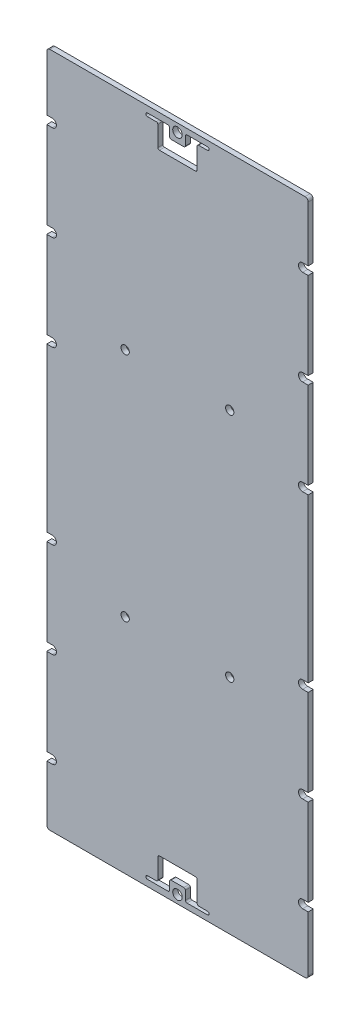
SolidWorks part; units mm, degrees
material "FR4_stuffedProtoboard"
ref_plane "Front Plane" through (0, 0, 0) normal (0, 0, 1) x (1, 0, 0)
ref_plane "Top Plane" through (0, 0, 0) normal (0, 1, 0) x (1, 0, 0)
ref_plane "Right Plane" through (0, 0, 0) normal (1, 0, 0) x (0, 0, -1)
sketch "Sketch1" plane through (0, 0, 0) normal (0, 0, 1) x (1, 0, 0)
  line L0 (-37, -97) -> (37, -97) construction
  line L5 (-37, -95.4) -> (37, -95.4) construction
  line L6 (-37, -87) -> (37, -87) construction
  line L7 (-37, -85.4) -> (37, -85.4) construction
  line L8 (-37, -77) -> (37, -77) construction
  line L9 (-37, -75.4) -> (37, -75.4) construction
  line L10 (-37, -67) -> (37, -67) construction
  line L11 (-37, -65.4) -> (37, -65.4) construction
  line L12 (-37, -57) -> (37, -57) construction
  line L13 (-37, -55.4) -> (37, -55.4) construction
  line L14 (-37, -47) -> (37, -47) construction
  line L15 (-37, -45.4) -> (37, -45.4) construction
  line L16 (-37, -37) -> (37, -37) construction
  line L17 (-37, -35.4) -> (37, -35.4) construction
  line L18 (-37, -27) -> (37, -27) construction
  line L19 (-37, -25.4) -> (37, -25.4) construction
  line L20 (-37, -17) -> (37, -17) construction
  line L21 (-37, -15.4) -> (37, -15.4) construction
  line L22 (-37, 15.4) -> (37, 15.4) construction
  line L23 (-37, 17) -> (37, 17) construction
  line L24 (-37, 25.4) -> (37, 25.4) construction
  line L25 (-37, 27) -> (37, 27) construction
  line L26 (-37, 35.4) -> (37, 35.4) construction
  line L27 (-37, 37) -> (37, 37) construction
  line L29 (-41.5, 107) -> (41.5, 107)
  line L30 (-41.5, 107) -> (-41.5, -107)
  line L31 (-41.5, -107) -> (41.5, -107)
  line L33 (41.5, 107) -> (41.5, -107)
  line L35 (-26.7, 107) -> (-28.3, 107) construction
  line L37 (-41.5, 109.5) -> (-41.5, 97.4) construction
  line L38 (41.5, 112.5) -> (41.5, 109.5) construction
  line L39 (-28.3, -107) -> (-26.7, -107) construction
  line L40 (-41.25, 106.75) -> (41.25, 106.75)
  line L41 (41.25, 106.75) -> (41.25, -106.75)
  line L42 (-41.25, -106.75) -> (41.25, -106.75)
  line L43 (-41.25, 106.75) -> (-41.25, -106.75)
  line L76 (-37, 45.4) -> (37, 45.4) construction
  line L77 (-37, 47) -> (37, 47) construction
  line L78 (-37, 55.4) -> (37, 55.4) construction
  line L79 (-37, 57) -> (37, 57) construction
  line L80 (-37, 65.4) -> (37, 65.4) construction
  line L81 (-37, 67) -> (37, 67) construction
  line L82 (-37, 75.4) -> (37, 75.4) construction
  line L83 (-37, 77) -> (37, 77) construction
  line L84 (-37, 85.4) -> (37, 85.4) construction
  line L85 (-37, 87) -> (37, 87) construction
  line L86 (-37, 95.4) -> (37, 95.4) construction
  line L87 (-37, 97) -> (37, 97) construction
  line L88 (-37, -97) -> (37, -97) construction
  line L89 (-37, -95.4) -> (37, -95.4) construction
  line L90 (-37, -87) -> (37, -87) construction
  line L91 (-37, -85.4) -> (37, -85.4) construction
  line L92 (-37, -77) -> (37, -77) construction
  line L93 (-37, -75.4) -> (37, -75.4) construction
  line L94 (-37, -67) -> (37, -67) construction
  line L95 (-37, -65.4) -> (37, -65.4) construction
  line L96 (-37, -57) -> (37, -57) construction
  line L97 (-37, -55.4) -> (37, -55.4) construction
  line L98 (-37, -47) -> (37, -47) construction
  line L99 (-37, -45.4) -> (37, -45.4) construction
  line L100 (-37, -37) -> (37, -37) construction
  line L101 (-37, -35.4) -> (37, -35.4) construction
  line L102 (-37, -27) -> (37, -27) construction
  line L103 (-37, -25.4) -> (37, -25.4) construction
  line L104 (-37, -17) -> (37, -17) construction
  line L105 (-37, -15.4) -> (37, -15.4) construction
  line L106 (-37, 15.4) -> (37, 15.4) construction
  line L107 (-37, 17) -> (37, 17) construction
  line L108 (-37, 25.4) -> (37, 25.4) construction
  line L109 (-37, 27) -> (37, 27) construction
  line L110 (-37, 35.4) -> (37, 35.4) construction
  line L111 (-37, 37) -> (37, 37) construction
  line L112 (-37, 45.4) -> (37, 45.4) construction
  line L113 (-37, 47) -> (37, 47) construction
  line L114 (-37, 55.4) -> (37, 55.4) construction
  line L115 (-37, 57) -> (37, 57) construction
  line L116 (-37, 65.4) -> (37, 65.4) construction
  line L117 (-37, 67) -> (37, 67) construction
  line L118 (-37, 75.4) -> (37, 75.4) construction
  line L119 (-37, 77) -> (37, 77) construction
  line L120 (-37, 85.4) -> (37, 85.4) construction
  line L121 (-37, 87) -> (37, 87) construction
  line L122 (-37, 95.4) -> (37, 95.4) construction
  line L123 (-37, 97) -> (37, 97) construction
  circle A0 centre (-39.5, 87) radius 0.8 construction
  circle A1 centre (-39.5, -27) radius 0.8 construction
  circle A2 centre (-39.5, 57) radius 0.8 construction
  circle A3 centre (39.5, -27) radius 0.8 construction
  circle A4 centre (-39.5, -27) radius 0.8
  circle A5 centre (-39.5, 27) radius 0.8 construction
  circle A6 centre (-16.5, 36.5) radius 0.8 construction
  circle A8 centre (39.5, -27) radius 0.8
  circle A9 centre (-16.5, -36.5) radius 0.8 construction
  circle A11 centre (-39.5, -57) radius 0.8 construction
  circle A13 centre (-39.5, -87) radius 0.8 construction
  circle A16 centre (0, -104.2) radius 0.8 construction
  circle A19 centre (39.5, -87) radius 0.8 construction
  circle A21 centre (39.5, -57) radius 0.8 construction
  circle A22 centre (16.5, -36.5) radius 0.8 construction
  circle A27 centre (39.5, 27) radius 0.8 construction
  circle A28 centre (16.5, 36.5) radius 0.8 construction
  circle A30 centre (39.5, 57) radius 0.8 construction
  circle A32 centre (39.5, 87) radius 0.8 construction
  circle A35 centre (0, 104.2) radius 0.8 construction
  circle A38 centre (-39.5, 87) radius 0.8
  circle A40 centre (-39.5, 57) radius 0.8
  circle A43 centre (-39.5, 27) radius 0.8
  circle A44 centre (-16.5, 36.5) radius 0.8
  circle A47 centre (-16.5, -36.5) radius 0.8
  circle A49 centre (-39.5, -57) radius 0.8
  circle A51 centre (-39.5, -87) radius 0.8
  circle A54 centre (0, -104.2) radius 0.8
  circle A57 centre (39.5, -87) radius 0.8
  circle A59 centre (39.5, -57) radius 0.8
  circle A60 centre (16.5, -36.5) radius 0.8
  circle A65 centre (39.5, 27) radius 0.8
  circle A66 centre (16.5, 36.5) radius 0.8
  circle A68 centre (39.5, 57) radius 0.8
  circle A70 centre (39.5, 87) radius 0.8
  circle A73 centre (0, 104.2) radius 0.8
  dimension "D1" = 0.25
extrude "pcb extrude" add sketch "Sketch1" along normal blind 1.6 contours A73 A70 A68 A66 A65 region at (0, 0, 0)
sketch "connector locations" plane through (0, 0, 1.6) normal (0, 0, 1) x (1, 0, 0)
  line L0 (-37, 97) -> (37, 97) construction
  line L1 (-33.9182, 100.556) -> (-9.2802, 100.556)
  line L2 (-33.9182, 100.556) -> (-33.9182, 99.159)
  line L3 (-33.9182, 99.159) -> (-9.2802, 99.159)
  line L4 (-9.2802, 100.556) -> (-9.2802, 99.159)
  line L5 (-33.9182, 100.556) -> (-9.2802, 99.159) construction
  line L6 (-33.9182, 99.159) -> (-9.2802, 100.556) construction
  line L7 (-37, 87) -> (37, 87) construction
  line L8 (-33.9182, 90.556) -> (-22.0818, 90.556)
  line L9 (-33.9182, 90.556) -> (-33.9182, 89.159)
  line L10 (-33.9182, 89.159) -> (-22.0818, 89.159)
  line L11 (-22.0818, 90.556) -> (-22.0818, 89.159)
  line L12 (-33.9182, 90.556) -> (-22.0818, 89.159) construction
  line L13 (-33.9182, 89.159) -> (-22.0818, 90.556) construction
  line L14 (0, -55) -> (0, 55) construction
  line L15 (-12.319, 90.556) -> (12.319, 90.556)
  line L16 (-12.319, 90.556) -> (-12.319, 89.159)
  line L17 (-12.319, 89.159) -> (12.319, 89.159)
  line L18 (12.319, 90.556) -> (12.319, 89.159)
  line L19 (-12.319, 90.556) -> (12.319, 89.159) construction
  line L20 (-12.319, 89.159) -> (12.319, 90.556) construction
  line L21 (-37, -85.4) -> (37, -85.4) construction
  line L22 (-33.9182, -91.844) -> (-9.2802, -91.844)
  line L23 (-33.9182, -91.844) -> (-33.9182, -93.241)
  line L24 (-33.9182, -93.241) -> (-9.2802, -93.241)
  line L25 (-9.2802, -91.844) -> (-9.2802, -93.241)
  line L26 (-33.9182, -91.844) -> (-9.2802, -93.241) construction
  line L27 (-33.9182, -93.241) -> (-9.2802, -91.844) construction
  line L28 (-33.9182, -81.844) -> (-22.0818, -81.844)
  line L29 (-33.9182, -81.844) -> (-33.9182, -83.241)
  line L30 (-33.9182, -83.241) -> (-22.0818, -83.241)
  line L31 (-22.0818, -81.844) -> (-22.0818, -83.241)
  line L32 (-33.9182, -81.844) -> (-22.0818, -83.241) construction
  line L33 (-33.9182, -83.241) -> (-22.0818, -81.844) construction
  line L34 (-12.319, -81.844) -> (12.319, -81.844)
  line L35 (-12.319, -81.844) -> (-12.319, -83.241)
  line L36 (-12.319, -83.241) -> (12.319, -83.241)
  line L37 (12.319, -81.844) -> (12.319, -83.241)
  line L38 (-12.319, -81.844) -> (12.319, -83.241) construction
  line L39 (-12.319, -83.241) -> (12.319, -81.844) construction
  line L40 (-37, -95.4) -> (37, -95.4) construction
  line L41 (-33.9182, 80.556) -> (-33.9182, 79.159)
  line L42 (-33.9182, 80.556) -> (-22.0818, 80.556)
  line L43 (-22.0818, 80.556) -> (-22.0818, 79.159)
  line L44 (-33.9182, 79.159) -> (-22.0818, 79.159)
  line L45 (-33.9182, 80.556) -> (-22.0818, 79.159) construction
  line L46 (-33.9182, 79.159) -> (-22.0818, 80.556) construction
  line L47 (-12.319, 80.556) -> (-12.319, 79.159)
  line L48 (-12.319, 80.556) -> (12.319, 80.556)
  line L49 (12.319, 80.556) -> (12.319, 79.159)
  line L50 (-12.319, 79.159) -> (12.319, 79.159)
  line L51 (-12.319, 80.556) -> (12.319, 79.159) construction
  line L52 (-12.319, 79.159) -> (12.319, 80.556) construction
  line L53 (-33.9182, 70.556) -> (-33.9182, 69.159)
  line L54 (-33.9182, 70.556) -> (-22.0818, 70.556)
  line L55 (-22.0818, 70.556) -> (-22.0818, 69.159)
  line L56 (-33.9182, 69.159) -> (-22.0818, 69.159)
  line L57 (-33.9182, 70.556) -> (-22.0818, 69.159) construction
  line L58 (-33.9182, 69.159) -> (-22.0818, 70.556) construction
  line L59 (-12.319, 70.556) -> (-12.319, 69.159)
  line L60 (-12.319, 70.556) -> (12.319, 70.556)
  line L61 (12.319, 70.556) -> (12.319, 69.159)
  line L62 (-12.319, 69.159) -> (12.319, 69.159)
  line L63 (-12.319, 70.556) -> (12.319, 69.159) construction
  line L64 (-12.319, 69.159) -> (12.319, 70.556) construction
  line L65 (-33.9182, 60.556) -> (-33.9182, 59.159)
  line L66 (-33.9182, 60.556) -> (-22.0818, 60.556)
  line L67 (-22.0818, 60.556) -> (-22.0818, 59.159)
  line L68 (-33.9182, 59.159) -> (-22.0818, 59.159)
  line L69 (-33.9182, 60.556) -> (-22.0818, 59.159) construction
  line L70 (-33.9182, 59.159) -> (-22.0818, 60.556) construction
  line L71 (-12.319, 60.556) -> (-12.319, 59.159)
  line L72 (-12.319, 60.556) -> (12.319, 60.556)
  line L73 (12.319, 60.556) -> (12.319, 59.159)
  line L74 (-12.319, 59.159) -> (12.319, 59.159)
  line L75 (-12.319, 60.556) -> (12.319, 59.159) construction
  line L76 (-12.319, 59.159) -> (12.319, 60.556) construction
  line L77 (-33.9182, 50.556) -> (-33.9182, 49.159)
  line L78 (-33.9182, 50.556) -> (-22.0818, 50.556)
  line L79 (-22.0818, 50.556) -> (-22.0818, 49.159)
  line L80 (-33.9182, 49.159) -> (-22.0818, 49.159)
  line L81 (-33.9182, 50.556) -> (-22.0818, 49.159) construction
  line L82 (-33.9182, 49.159) -> (-22.0818, 50.556) construction
  line L83 (-12.319, 50.556) -> (-12.319, 49.159)
  line L84 (-12.319, 50.556) -> (12.319, 50.556)
  line L85 (12.319, 50.556) -> (12.319, 49.159)
  line L86 (-12.319, 49.159) -> (12.319, 49.159)
  line L87 (-12.319, 50.556) -> (12.319, 49.159) construction
  line L88 (-12.319, 49.159) -> (12.319, 50.556) construction
  line L89 (-33.9182, 40.556) -> (-33.9182, 39.159)
  line L90 (-33.9182, 40.556) -> (-22.0818, 40.556)
  line L91 (-22.0818, 40.556) -> (-22.0818, 39.159)
  line L92 (-33.9182, 39.159) -> (-22.0818, 39.159)
  line L93 (-33.9182, 40.556) -> (-22.0818, 39.159) construction
  line L94 (-33.9182, 39.159) -> (-22.0818, 40.556) construction
  line L95 (-12.319, 40.556) -> (-12.319, 39.159)
  line L96 (-12.319, 40.556) -> (12.319, 40.556)
  line L97 (12.319, 40.556) -> (12.319, 39.159)
  line L98 (-12.319, 39.159) -> (12.319, 39.159)
  line L99 (-12.319, 40.556) -> (12.319, 39.159) construction
  line L100 (-12.319, 39.159) -> (12.319, 40.556) construction
  line L101 (-33.9182, 30.556) -> (-33.9182, 29.159)
  line L102 (-33.9182, 30.556) -> (-22.0818, 30.556)
  line L103 (-22.0818, 30.556) -> (-22.0818, 29.159)
  line L104 (-33.9182, 29.159) -> (-22.0818, 29.159)
  line L105 (-33.9182, 30.556) -> (-22.0818, 29.159) construction
  line L106 (-33.9182, 29.159) -> (-22.0818, 30.556) construction
  line L107 (-12.319, 30.556) -> (-12.319, 29.159)
  line L108 (-12.319, 30.556) -> (12.319, 30.556)
  line L109 (12.319, 30.556) -> (12.319, 29.159)
  line L110 (-12.319, 29.159) -> (12.319, 29.159)
  line L111 (-12.319, 30.556) -> (12.319, 29.159) construction
  line L112 (-12.319, 29.159) -> (12.319, 30.556) construction
  line L113 (-33.9182, 20.556) -> (-33.9182, 19.159)
  line L114 (-33.9182, 20.556) -> (-22.0818, 20.556)
  line L115 (-22.0818, 20.556) -> (-22.0818, 19.159)
  line L116 (-33.9182, 19.159) -> (-22.0818, 19.159)
  line L117 (-33.9182, 20.556) -> (-22.0818, 19.159) construction
  line L118 (-33.9182, 19.159) -> (-22.0818, 20.556) construction
  line L119 (-12.319, 20.556) -> (-12.319, 19.159)
  line L120 (-12.319, 20.556) -> (12.319, 20.556)
  line L121 (12.319, 20.556) -> (12.319, 19.159)
  line L122 (-12.319, 19.159) -> (12.319, 19.159)
  line L123 (-12.319, 20.556) -> (12.319, 19.159) construction
  line L124 (-12.319, 19.159) -> (12.319, 20.556) construction
  line L125 (-33.9182, 10.556) -> (-33.9182, 9.159)
  line L126 (-33.9182, 10.556) -> (-22.0818, 10.556)
  line L127 (-22.0818, 10.556) -> (-22.0818, 9.159)
  line L128 (-33.9182, 9.159) -> (-22.0818, 9.159)
  line L129 (-33.9182, 10.556) -> (-22.0818, 9.159) construction
  line L130 (-33.9182, 9.159) -> (-22.0818, 10.556) construction
  line L131 (-12.319, 10.556) -> (-12.319, 9.159)
  line L132 (-12.319, 10.556) -> (12.319, 10.556)
  line L133 (12.319, 10.556) -> (12.319, 9.159)
  line L134 (-12.319, 9.159) -> (12.319, 9.159)
  line L135 (-12.319, 10.556) -> (12.319, 9.159) construction
  line L136 (-12.319, 9.159) -> (12.319, 10.556) construction
  line L137 (0, 89.8575) -> (0, 79.8575) construction
  line L138 (-33.9182, -71.844) -> (-33.9182, -73.241)
  line L139 (-33.9182, -71.844) -> (-22.0818, -71.844)
  line L140 (-22.0818, -71.844) -> (-22.0818, -73.241)
  line L141 (-33.9182, -73.241) -> (-22.0818, -73.241)
  line L142 (-33.9182, -73.241) -> (-22.0818, -71.844) construction
  line L143 (-33.9182, -71.844) -> (-22.0818, -73.241) construction
  line L144 (-12.319, -71.844) -> (-12.319, -73.241)
  line L145 (-12.319, -71.844) -> (12.319, -71.844)
  line L146 (12.319, -71.844) -> (12.319, -73.241)
  line L147 (-12.319, -73.241) -> (12.319, -73.241)
  line L148 (-12.319, -73.241) -> (12.319, -71.844) construction
  line L149 (-12.319, -71.844) -> (12.319, -73.241) construction
  line L150 (-33.9182, -61.844) -> (-33.9182, -63.241)
  line L151 (-33.9182, -61.844) -> (-22.0818, -61.844)
  line L152 (-22.0818, -61.844) -> (-22.0818, -63.241)
  line L153 (-33.9182, -63.241) -> (-22.0818, -63.241)
  line L154 (-33.9182, -63.241) -> (-22.0818, -61.844) construction
  line L155 (-33.9182, -61.844) -> (-22.0818, -63.241) construction
  line L156 (-12.319, -61.844) -> (-12.319, -63.241)
  line L157 (-12.319, -61.844) -> (12.319, -61.844)
  line L158 (12.319, -61.844) -> (12.319, -63.241)
  line L159 (-12.319, -63.241) -> (12.319, -63.241)
  line L160 (-12.319, -63.241) -> (12.319, -61.844) construction
  line L161 (-12.319, -61.844) -> (12.319, -63.241) construction
  line L162 (-33.9182, -51.844) -> (-33.9182, -53.241)
  line L163 (-33.9182, -51.844) -> (-22.0818, -51.844)
  line L164 (-22.0818, -51.844) -> (-22.0818, -53.241)
  line L165 (-33.9182, -53.241) -> (-22.0818, -53.241)
  line L166 (-33.9182, -53.241) -> (-22.0818, -51.844) construction
  line L167 (-33.9182, -51.844) -> (-22.0818, -53.241) construction
  line L168 (-12.319, -51.844) -> (-12.319, -53.241)
  line L169 (-12.319, -51.844) -> (12.319, -51.844)
  line L170 (12.319, -51.844) -> (12.319, -53.241)
  line L171 (-12.319, -53.241) -> (12.319, -53.241)
  line L172 (-12.319, -53.241) -> (12.319, -51.844) construction
  line L173 (-12.319, -51.844) -> (12.319, -53.241) construction
  line L174 (-33.9182, -41.844) -> (-33.9182, -43.241)
  line L175 (-33.9182, -41.844) -> (-22.0818, -41.844)
  line L176 (-22.0818, -41.844) -> (-22.0818, -43.241)
  line L177 (-33.9182, -43.241) -> (-22.0818, -43.241)
  line L178 (-33.9182, -43.241) -> (-22.0818, -41.844) construction
  line L179 (-33.9182, -41.844) -> (-22.0818, -43.241) construction
  line L180 (-12.319, -41.844) -> (-12.319, -43.241)
  line L181 (-12.319, -41.844) -> (12.319, -41.844)
  line L182 (12.319, -41.844) -> (12.319, -43.241)
  line L183 (-12.319, -43.241) -> (12.319, -43.241)
  line L184 (-12.319, -43.241) -> (12.319, -41.844) construction
  line L185 (-12.319, -41.844) -> (12.319, -43.241) construction
  line L186 (-33.9182, -31.844) -> (-33.9182, -33.241)
  line L187 (-33.9182, -31.844) -> (-22.0818, -31.844)
  line L188 (-22.0818, -31.844) -> (-22.0818, -33.241)
  line L189 (-33.9182, -33.241) -> (-22.0818, -33.241)
  line L190 (-33.9182, -33.241) -> (-22.0818, -31.844) construction
  line L191 (-33.9182, -31.844) -> (-22.0818, -33.241) construction
  line L192 (-12.319, -31.844) -> (-12.319, -33.241)
  line L193 (-12.319, -31.844) -> (12.319, -31.844)
  line L194 (12.319, -31.844) -> (12.319, -33.241)
  line L195 (-12.319, -33.241) -> (12.319, -33.241)
  line L196 (-12.319, -33.241) -> (12.319, -31.844) construction
  line L197 (-12.319, -31.844) -> (12.319, -33.241) construction
  line L198 (-33.9182, -21.844) -> (-33.9182, -23.241)
  line L199 (-33.9182, -21.844) -> (-22.0818, -21.844)
  line L200 (-22.0818, -21.844) -> (-22.0818, -23.241)
  line L201 (-33.9182, -23.241) -> (-22.0818, -23.241)
  line L202 (-33.9182, -23.241) -> (-22.0818, -21.844) construction
  line L203 (-33.9182, -21.844) -> (-22.0818, -23.241) construction
  line L204 (-12.319, -21.844) -> (-12.319, -23.241)
  line L205 (-12.319, -21.844) -> (12.319, -21.844)
  line L206 (12.319, -21.844) -> (12.319, -23.241)
  line L207 (-12.319, -23.241) -> (12.319, -23.241)
  line L208 (-12.319, -23.241) -> (12.319, -21.844) construction
  line L209 (-12.319, -21.844) -> (12.319, -23.241) construction
  line L210 (-33.9182, -11.844) -> (-33.9182, -13.241)
  line L211 (-33.9182, -11.844) -> (-22.0818, -11.844)
  line L212 (-22.0818, -11.844) -> (-22.0818, -13.241)
  line L213 (-33.9182, -13.241) -> (-22.0818, -13.241)
  line L214 (-33.9182, -13.241) -> (-22.0818, -11.844) construction
  line L215 (-33.9182, -11.844) -> (-22.0818, -13.241) construction
  line L216 (-12.319, -11.844) -> (-12.319, -13.241)
  line L217 (-12.319, -11.844) -> (12.319, -11.844)
  line L218 (12.319, -11.844) -> (12.319, -13.241)
  line L219 (-12.319, -13.241) -> (12.319, -13.241)
  line L220 (-12.319, -13.241) -> (12.319, -11.844) construction
  line L221 (-12.319, -11.844) -> (12.319, -13.241) construction
  line L222 (-33.9182, -1.844) -> (-33.9182, -3.241)
  line L223 (-33.9182, -1.844) -> (-22.0818, -1.844)
  line L224 (-22.0818, -1.844) -> (-22.0818, -3.241)
  line L225 (-33.9182, -3.241) -> (-22.0818, -3.241)
  line L226 (-33.9182, -3.241) -> (-22.0818, -1.844) construction
  line L227 (-33.9182, -1.844) -> (-22.0818, -3.241) construction
  line L228 (-12.319, -1.844) -> (-12.319, -3.241)
  line L229 (-12.319, -1.844) -> (12.319, -1.844)
  line L230 (12.319, -1.844) -> (12.319, -3.241)
  line L231 (-12.319, -3.241) -> (12.319, -3.241)
  line L232 (-12.319, -3.241) -> (12.319, -1.844) construction
  line L233 (-12.319, -1.844) -> (12.319, -3.241) construction
  line L234 (0, -82.5425) -> (0, -72.5425) construction
  line L235 (26.92, 96.09) -> (29.08, 98.27) construction
  line L236 (26.92, 98.27) -> (29.08, 96.09) construction
  line L237 (32.92, 98.27) -> (35.08, 96.09) construction
  line L238 (32.92, 96.09) -> (35.08, 98.27) construction
  line L239 (20.92, 96.09) -> (23.08, 98.27) construction
  line L240 (20.92, 98.27) -> (23.08, 96.09) construction
  line L241 (26.92, 86.09) -> (29.08, 88.27) construction
  line L242 (26.92, 88.27) -> (29.08, 86.09) construction
  line L243 (20.92, 86.09) -> (23.08, 88.27) construction
  line L244 (20.92, 88.27) -> (23.08, 86.09) construction
  line L245 (26.92, 76.09) -> (29.08, 78.27) construction
  line L246 (26.92, 78.27) -> (29.08, 76.09) construction
  line L247 (20.92, 76.09) -> (23.08, 78.27) construction
  line L248 (20.92, 78.27) -> (23.08, 76.09) construction
  line L249 (26.92, 66.09) -> (29.08, 68.27) construction
  line L250 (26.92, 68.27) -> (29.08, 66.09) construction
  line L251 (20.92, 66.09) -> (23.08, 68.27) construction
  line L252 (20.92, 68.27) -> (23.08, 66.09) construction
  line L253 (26.92, 56.09) -> (29.08, 58.27) construction
  line L254 (26.92, 58.27) -> (29.08, 56.09) construction
  line L255 (20.92, 56.09) -> (23.08, 58.27) construction
  line L256 (20.92, 58.27) -> (23.08, 56.09) construction
  line L257 (26.92, 46.09) -> (29.08, 48.27) construction
  line L258 (26.92, 48.27) -> (29.08, 46.09) construction
  line L259 (20.92, 46.09) -> (23.08, 48.27) construction
  line L260 (20.92, 48.27) -> (23.08, 46.09) construction
  line L261 (26.92, 36.09) -> (29.08, 38.27) construction
  line L262 (26.92, 38.27) -> (29.08, 36.09) construction
  line L263 (20.92, 36.09) -> (23.08, 38.27) construction
  line L264 (20.92, 38.27) -> (23.08, 36.09) construction
  line L265 (26.92, 26.09) -> (29.08, 28.27) construction
  line L266 (26.92, 28.27) -> (29.08, 26.09) construction
  line L267 (20.92, 26.09) -> (23.08, 28.27) construction
  line L268 (20.92, 28.27) -> (23.08, 26.09) construction
  line L269 (26.92, 16.09) -> (29.08, 18.27) construction
  line L270 (26.92, 18.27) -> (29.08, 16.09) construction
  line L271 (20.92, 16.09) -> (23.08, 18.27) construction
  line L272 (20.92, 18.27) -> (23.08, 16.09) construction
  line L273 (26.92, 6.09) -> (29.08, 8.27) construction
  line L274 (26.92, 8.27) -> (29.08, 6.09) construction
  line L275 (20.92, 6.09) -> (23.08, 8.27) construction
  line L276 (20.92, 8.27) -> (23.08, 6.09) construction
  line L277 (32.92, 86.09) -> (35.08, 88.27) construction
  line L278 (32.92, 88.27) -> (35.08, 86.09) construction
  line L279 (32.92, 76.09) -> (35.08, 78.27) construction
  line L280 (32.92, 78.27) -> (35.08, 76.09) construction
  line L281 (32.92, 66.09) -> (35.08, 68.27) construction
  line L282 (32.92, 68.27) -> (35.08, 66.09) construction
  line L283 (32.92, 56.09) -> (35.08, 58.27) construction
  line L284 (32.92, 58.27) -> (35.08, 56.09) construction
  line L285 (32.92, 46.09) -> (35.08, 48.27) construction
  line L286 (32.92, 48.27) -> (35.08, 46.09) construction
  line L287 (32.92, 36.09) -> (35.08, 38.27) construction
  line L288 (32.92, 38.27) -> (35.08, 36.09) construction
  line L289 (32.92, 26.09) -> (35.08, 28.27) construction
  line L290 (32.92, 28.27) -> (35.08, 26.09) construction
  line L291 (32.92, 16.09) -> (35.08, 18.27) construction
  line L292 (32.92, 18.27) -> (35.08, 16.09) construction
  line L293 (32.92, 6.09) -> (35.08, 8.27) construction
  line L294 (32.92, 8.27) -> (35.08, 6.09) construction
  line L295 (32.92, 98.27) -> (26.92, 98.27) construction
  line L296 (32.92, 98.27) -> (32.92, 88.27) construction
  line L297 (32.92, -94.13) -> (35.08, -96.31) construction
  line L298 (35.08, -94.13) -> (32.92, -96.31) construction
  line L299 (29.08, -94.13) -> (26.92, -96.31) construction
  line L300 (26.92, -94.13) -> (29.08, -96.31) construction
  line L301 (23.08, -94.13) -> (20.92, -96.31) construction
  line L302 (20.92, -94.13) -> (23.08, -96.31) construction
  line L303 (29.08, -84.13) -> (26.92, -86.31) construction
  line L304 (26.92, -84.13) -> (29.08, -86.31) construction
  line L305 (23.08, -84.13) -> (20.92, -86.31) construction
  line L306 (20.92, -84.13) -> (23.08, -86.31) construction
  line L307 (29.08, -74.13) -> (26.92, -76.31) construction
  line L308 (26.92, -74.13) -> (29.08, -76.31) construction
  line L309 (23.08, -74.13) -> (20.92, -76.31) construction
  line L310 (20.92, -74.13) -> (23.08, -76.31) construction
  line L311 (29.08, -64.13) -> (26.92, -66.31) construction
  line L312 (26.92, -64.13) -> (29.08, -66.31) construction
  line L313 (23.08, -64.13) -> (20.92, -66.31) construction
  line L314 (20.92, -64.13) -> (23.08, -66.31) construction
  line L315 (29.08, -54.13) -> (26.92, -56.31) construction
  line L316 (26.92, -54.13) -> (29.08, -56.31) construction
  line L317 (23.08, -54.13) -> (20.92, -56.31) construction
  line L318 (20.92, -54.13) -> (23.08, -56.31) construction
  line L319 (29.08, -44.13) -> (26.92, -46.31) construction
  line L320 (26.92, -44.13) -> (29.08, -46.31) construction
  line L321 (23.08, -44.13) -> (20.92, -46.31) construction
  line L322 (20.92, -44.13) -> (23.08, -46.31) construction
  line L323 (29.08, -34.13) -> (26.92, -36.31) construction
  line L324 (26.92, -34.13) -> (29.08, -36.31) construction
  line L325 (23.08, -34.13) -> (20.92, -36.31) construction
  line L326 (20.92, -34.13) -> (23.08, -36.31) construction
  line L327 (29.08, -24.13) -> (26.92, -26.31) construction
  line L328 (26.92, -24.13) -> (29.08, -26.31) construction
  line L329 (23.08, -24.13) -> (20.92, -26.31) construction
  line L330 (20.92, -24.13) -> (23.08, -26.31) construction
  line L331 (29.08, -14.13) -> (26.92, -16.31) construction
  line L332 (26.92, -14.13) -> (29.08, -16.31) construction
  line L333 (23.08, -14.13) -> (20.92, -16.31) construction
  line L334 (20.92, -14.13) -> (23.08, -16.31) construction
  line L335 (29.08, -4.13) -> (26.92, -6.31) construction
  line L336 (26.92, -4.13) -> (29.08, -6.31) construction
  line L337 (23.08, -4.13) -> (20.92, -6.31) construction
  line L338 (20.92, -4.13) -> (23.08, -6.31) construction
  line L339 (35.08, -84.13) -> (32.92, -86.31) construction
  line L340 (32.92, -84.13) -> (35.08, -86.31) construction
  line L341 (35.08, -74.13) -> (32.92, -76.31) construction
  line L342 (32.92, -74.13) -> (35.08, -76.31) construction
  line L343 (35.08, -64.13) -> (32.92, -66.31) construction
  line L344 (32.92, -64.13) -> (35.08, -66.31) construction
  line L345 (35.08, -54.13) -> (32.92, -56.31) construction
  line L346 (32.92, -54.13) -> (35.08, -56.31) construction
  line L347 (35.08, -44.13) -> (32.92, -46.31) construction
  line L348 (32.92, -44.13) -> (35.08, -46.31) construction
  line L349 (35.08, -34.13) -> (32.92, -36.31) construction
  line L350 (32.92, -34.13) -> (35.08, -36.31) construction
  line L351 (35.08, -24.13) -> (32.92, -26.31) construction
  line L352 (32.92, -24.13) -> (35.08, -26.31) construction
  line L353 (35.08, -14.13) -> (32.92, -16.31) construction
  line L354 (32.92, -14.13) -> (35.08, -16.31) construction
  line L355 (35.08, -4.13) -> (32.92, -6.31) construction
  line L356 (32.92, -4.13) -> (35.08, -6.31) construction
  line L357 (32.92, -94.13) -> (26.92, -94.13) construction
  line L358 (32.92, -94.13) -> (32.92, -84.13) construction
  line L359 (-28, 89.8575) -> (-28, 79.8575) construction
  line L360 (-28, -82.5425) -> (-28, -72.5425) construction
  line L361 (-37, 100.5) -> (-37, -100.5) construction
  line L362 (-34.5, -103) -> (-4.5, -103) construction
  line L363 (-2.5, -102) -> (2.5, -102) construction
  line L364 (4.5, -103) -> (34.5, -103) construction
  line L365 (37, -100.5) -> (37, 100.5) construction
  line L366 (34.5, 103) -> (4.5, 103) construction
  line L367 (-2.5, 102) -> (2.5, 102) construction
  line L368 (-4.5, 103) -> (-34.5, 103) construction
  line L369 (-37, 100.5) -> (-37, -100.5)
  line L370 (-34.5, -103) -> (-4.5, -103)
  line L371 (-2.5, -102) -> (2.5, -102)
  line L372 (4.5, -103) -> (34.5, -103)
  line L373 (37, -100.5) -> (37, 100.5)
  line L374 (34.5, 103) -> (4.5, 103)
  line L375 (-2.5, 102) -> (2.5, 102)
  line L376 (-4.5, 103) -> (-34.5, 103)
  circle A0 centre (32.92, 98.27) radius 0.32
  circle A1 centre (35.08, 98.27) radius 0.32
  circle A2 centre (35.08, 96.09) radius 0.32
  circle A3 centre (32.92, 96.09) radius 0.32
  circle A4 centre (26.92, 98.27) radius 0.32
  circle A5 centre (29.08, 98.27) radius 0.32
  circle A6 centre (29.08, 96.09) radius 0.32
  circle A7 centre (26.92, 96.09) radius 0.32
  circle A8 centre (20.92, 98.27) radius 0.32
  circle A9 centre (23.08, 98.27) radius 0.32
  circle A10 centre (23.08, 96.09) radius 0.32
  circle A11 centre (20.92, 96.09) radius 0.32
  circle A12 centre (26.92, 88.27) radius 0.32
  circle A13 centre (29.08, 88.27) radius 0.32
  circle A14 centre (29.08, 86.09) radius 0.32
  circle A15 centre (26.92, 86.09) radius 0.32
  circle A16 centre (20.92, 88.27) radius 0.32
  circle A17 centre (23.08, 88.27) radius 0.32
  circle A18 centre (23.08, 86.09) radius 0.32
  circle A19 centre (20.92, 86.09) radius 0.32
  circle A20 centre (26.92, 78.27) radius 0.32
  circle A21 centre (29.08, 78.27) radius 0.32
  circle A22 centre (29.08, 76.09) radius 0.32
  circle A23 centre (26.92, 76.09) radius 0.32
  circle A24 centre (20.92, 78.27) radius 0.32
  circle A25 centre (23.08, 78.27) radius 0.32
  circle A26 centre (23.08, 76.09) radius 0.32
  circle A27 centre (20.92, 76.09) radius 0.32
  circle A28 centre (26.92, 68.27) radius 0.32
  circle A29 centre (29.08, 68.27) radius 0.32
  circle A30 centre (29.08, 66.09) radius 0.32
  circle A31 centre (26.92, 66.09) radius 0.32
  circle A32 centre (20.92, 68.27) radius 0.32
  circle A33 centre (23.08, 68.27) radius 0.32
  circle A34 centre (23.08, 66.09) radius 0.32
  circle A35 centre (20.92, 66.09) radius 0.32
  circle A36 centre (26.92, 58.27) radius 0.32
  circle A37 centre (29.08, 58.27) radius 0.32
  circle A38 centre (29.08, 56.09) radius 0.32
  circle A39 centre (26.92, 56.09) radius 0.32
  circle A40 centre (20.92, 58.27) radius 0.32
  circle A41 centre (23.08, 58.27) radius 0.32
  circle A42 centre (23.08, 56.09) radius 0.32
  circle A43 centre (20.92, 56.09) radius 0.32
  circle A44 centre (26.92, 48.27) radius 0.32
  circle A45 centre (29.08, 48.27) radius 0.32
  circle A46 centre (29.08, 46.09) radius 0.32
  circle A47 centre (26.92, 46.09) radius 0.32
  circle A48 centre (20.92, 48.27) radius 0.32
  circle A49 centre (23.08, 48.27) radius 0.32
  circle A50 centre (23.08, 46.09) radius 0.32
  circle A51 centre (20.92, 46.09) radius 0.32
  circle A52 centre (26.92, 38.27) radius 0.32
  circle A53 centre (29.08, 38.27) radius 0.32
  circle A54 centre (29.08, 36.09) radius 0.32
  circle A55 centre (26.92, 36.09) radius 0.32
  circle A56 centre (20.92, 38.27) radius 0.32
  circle A57 centre (23.08, 38.27) radius 0.32
  circle A58 centre (23.08, 36.09) radius 0.32
  circle A59 centre (20.92, 36.09) radius 0.32
  circle A60 centre (26.92, 28.27) radius 0.32
  circle A61 centre (29.08, 28.27) radius 0.32
  circle A62 centre (29.08, 26.09) radius 0.32
  circle A63 centre (26.92, 26.09) radius 0.32
  circle A64 centre (20.92, 28.27) radius 0.32
  circle A65 centre (23.08, 28.27) radius 0.32
  circle A66 centre (23.08, 26.09) radius 0.32
  circle A67 centre (20.92, 26.09) radius 0.32
  circle A68 centre (26.92, 18.27) radius 0.32
  circle A69 centre (29.08, 18.27) radius 0.32
  circle A70 centre (29.08, 16.09) radius 0.32
  circle A71 centre (26.92, 16.09) radius 0.32
  circle A72 centre (20.92, 18.27) radius 0.32
  circle A73 centre (23.08, 18.27) radius 0.32
  circle A74 centre (23.08, 16.09) radius 0.32
  circle A75 centre (20.92, 16.09) radius 0.32
  circle A76 centre (26.92, 8.27) radius 0.32
  circle A77 centre (29.08, 8.27) radius 0.32
  circle A78 centre (29.08, 6.09) radius 0.32
  circle A79 centre (26.92, 6.09) radius 0.32
  circle A80 centre (20.92, 8.27) radius 0.32
  circle A81 centre (23.08, 8.27) radius 0.32
  circle A82 centre (23.08, 6.09) radius 0.32
  circle A83 centre (20.92, 6.09) radius 0.32
  circle A84 centre (32.92, 88.27) radius 0.32
  circle A85 centre (35.08, 88.27) radius 0.32
  circle A86 centre (35.08, 86.09) radius 0.32
  circle A87 centre (32.92, 86.09) radius 0.32
  circle A88 centre (32.92, 78.27) radius 0.32
  circle A89 centre (35.08, 78.27) radius 0.32
  circle A90 centre (35.08, 76.09) radius 0.32
  circle A91 centre (32.92, 76.09) radius 0.32
  circle A92 centre (32.92, 68.27) radius 0.32
  circle A93 centre (35.08, 68.27) radius 0.32
  circle A94 centre (35.08, 66.09) radius 0.32
  circle A95 centre (32.92, 66.09) radius 0.32
  circle A96 centre (32.92, 58.27) radius 0.32
  circle A97 centre (35.08, 58.27) radius 0.32
  circle A98 centre (35.08, 56.09) radius 0.32
  circle A99 centre (32.92, 56.09) radius 0.32
  circle A100 centre (32.92, 48.27) radius 0.32
  circle A101 centre (35.08, 48.27) radius 0.32
  circle A102 centre (35.08, 46.09) radius 0.32
  circle A103 centre (32.92, 46.09) radius 0.32
  circle A104 centre (32.92, 38.27) radius 0.32
  circle A105 centre (35.08, 38.27) radius 0.32
  circle A106 centre (35.08, 36.09) radius 0.32
  circle A107 centre (32.92, 36.09) radius 0.32
  circle A108 centre (32.92, 28.27) radius 0.32
  circle A109 centre (35.08, 28.27) radius 0.32
  circle A110 centre (35.08, 26.09) radius 0.32
  circle A111 centre (32.92, 26.09) radius 0.32
  circle A112 centre (32.92, 18.27) radius 0.32
  circle A113 centre (35.08, 18.27) radius 0.32
  circle A114 centre (35.08, 16.09) radius 0.32
  circle A115 centre (32.92, 16.09) radius 0.32
  circle A116 centre (32.92, 8.27) radius 0.32
  circle A117 centre (35.08, 8.27) radius 0.32
  circle A118 centre (35.08, 6.09) radius 0.32
  circle A119 centre (32.92, 6.09) radius 0.32
  circle A120 centre (35.08, -94.13) radius 0.32
  circle A121 centre (32.92, -94.13) radius 0.32
  circle A122 centre (32.92, -96.31) radius 0.32
  circle A123 centre (35.08, -96.31) radius 0.32
  circle A124 centre (26.92, -94.13) radius 0.32
  circle A125 centre (29.08, -94.13) radius 0.32
  circle A126 centre (29.08, -96.31) radius 0.32
  circle A127 centre (26.92, -96.31) radius 0.32
  circle A128 centre (20.92, -94.13) radius 0.32
  circle A129 centre (23.08, -94.13) radius 0.32
  circle A130 centre (23.08, -96.31) radius 0.32
  circle A131 centre (20.92, -96.31) radius 0.32
  circle A132 centre (26.92, -84.13) radius 0.32
  circle A133 centre (29.08, -84.13) radius 0.32
  circle A134 centre (29.08, -86.31) radius 0.32
  circle A135 centre (26.92, -86.31) radius 0.32
  circle A136 centre (20.92, -84.13) radius 0.32
  circle A137 centre (23.08, -84.13) radius 0.32
  circle A138 centre (23.08, -86.31) radius 0.32
  circle A139 centre (20.92, -86.31) radius 0.32
  circle A140 centre (26.92, -74.13) radius 0.32
  circle A141 centre (29.08, -74.13) radius 0.32
  circle A142 centre (29.08, -76.31) radius 0.32
  circle A143 centre (26.92, -76.31) radius 0.32
  circle A144 centre (20.92, -74.13) radius 0.32
  circle A145 centre (23.08, -74.13) radius 0.32
  circle A146 centre (23.08, -76.31) radius 0.32
  circle A147 centre (20.92, -76.31) radius 0.32
  circle A148 centre (26.92, -64.13) radius 0.32
  circle A149 centre (29.08, -64.13) radius 0.32
  circle A150 centre (29.08, -66.31) radius 0.32
  circle A151 centre (26.92, -66.31) radius 0.32
  circle A152 centre (20.92, -64.13) radius 0.32
  circle A153 centre (23.08, -64.13) radius 0.32
  circle A154 centre (23.08, -66.31) radius 0.32
  circle A155 centre (20.92, -66.31) radius 0.32
  circle A156 centre (26.92, -54.13) radius 0.32
  circle A157 centre (29.08, -54.13) radius 0.32
  circle A158 centre (29.08, -56.31) radius 0.32
  circle A159 centre (26.92, -56.31) radius 0.32
  circle A160 centre (20.92, -54.13) radius 0.32
  circle A161 centre (23.08, -54.13) radius 0.32
  circle A162 centre (23.08, -56.31) radius 0.32
  circle A163 centre (20.92, -56.31) radius 0.32
  circle A164 centre (26.92, -44.13) radius 0.32
  circle A165 centre (29.08, -44.13) radius 0.32
  circle A166 centre (29.08, -46.31) radius 0.32
  circle A167 centre (26.92, -46.31) radius 0.32
  circle A168 centre (20.92, -44.13) radius 0.32
  circle A169 centre (23.08, -44.13) radius 0.32
  circle A170 centre (23.08, -46.31) radius 0.32
  circle A171 centre (20.92, -46.31) radius 0.32
  circle A172 centre (26.92, -34.13) radius 0.32
  circle A173 centre (29.08, -34.13) radius 0.32
  circle A174 centre (29.08, -36.31) radius 0.32
  circle A175 centre (26.92, -36.31) radius 0.32
  circle A176 centre (20.92, -34.13) radius 0.32
  circle A177 centre (23.08, -34.13) radius 0.32
  circle A178 centre (23.08, -36.31) radius 0.32
  circle A179 centre (20.92, -36.31) radius 0.32
  circle A180 centre (26.92, -24.13) radius 0.32
  circle A181 centre (29.08, -24.13) radius 0.32
  circle A182 centre (29.08, -26.31) radius 0.32
  circle A183 centre (26.92, -26.31) radius 0.32
  circle A184 centre (20.92, -24.13) radius 0.32
  circle A185 centre (23.08, -24.13) radius 0.32
  circle A186 centre (23.08, -26.31) radius 0.32
  circle A187 centre (20.92, -26.31) radius 0.32
  circle A188 centre (26.92, -14.13) radius 0.32
  circle A189 centre (29.08, -14.13) radius 0.32
  circle A190 centre (29.08, -16.31) radius 0.32
  circle A191 centre (26.92, -16.31) radius 0.32
  circle A192 centre (20.92, -14.13) radius 0.32
  circle A193 centre (23.08, -14.13) radius 0.32
  circle A194 centre (23.08, -16.31) radius 0.32
  circle A195 centre (20.92, -16.31) radius 0.32
  circle A196 centre (26.92, -4.13) radius 0.32
  circle A197 centre (29.08, -4.13) radius 0.32
  circle A198 centre (29.08, -6.31) radius 0.32
  circle A199 centre (26.92, -6.31) radius 0.32
  circle A200 centre (20.92, -4.13) radius 0.32
  circle A201 centre (23.08, -4.13) radius 0.32
  circle A202 centre (23.08, -6.31) radius 0.32
  circle A203 centre (20.92, -6.31) radius 0.32
  circle A204 centre (32.92, -84.13) radius 0.32
  circle A205 centre (35.08, -84.13) radius 0.32
  circle A206 centre (35.08, -86.31) radius 0.32
  circle A207 centre (32.92, -86.31) radius 0.32
  circle A208 centre (32.92, -74.13) radius 0.32
  circle A209 centre (35.08, -74.13) radius 0.32
  circle A210 centre (35.08, -76.31) radius 0.32
  circle A211 centre (32.92, -76.31) radius 0.32
  circle A212 centre (32.92, -64.13) radius 0.32
  circle A213 centre (35.08, -64.13) radius 0.32
  circle A214 centre (35.08, -66.31) radius 0.32
  circle A215 centre (32.92, -66.31) radius 0.32
  circle A216 centre (32.92, -54.13) radius 0.32
  circle A217 centre (35.08, -54.13) radius 0.32
  circle A218 centre (35.08, -56.31) radius 0.32
  circle A219 centre (32.92, -56.31) radius 0.32
  circle A220 centre (32.92, -44.13) radius 0.32
  circle A221 centre (35.08, -44.13) radius 0.32
  circle A222 centre (35.08, -46.31) radius 0.32
  circle A223 centre (32.92, -46.31) radius 0.32
  circle A224 centre (32.92, -34.13) radius 0.32
  circle A225 centre (35.08, -34.13) radius 0.32
  circle A226 centre (35.08, -36.31) radius 0.32
  circle A227 centre (32.92, -36.31) radius 0.32
  circle A228 centre (32.92, -24.13) radius 0.32
  circle A229 centre (35.08, -24.13) radius 0.32
  circle A230 centre (35.08, -26.31) radius 0.32
  circle A231 centre (32.92, -26.31) radius 0.32
  circle A232 centre (32.92, -14.13) radius 0.32
  circle A233 centre (35.08, -14.13) radius 0.32
  circle A234 centre (35.08, -16.31) radius 0.32
  circle A235 centre (32.92, -16.31) radius 0.32
  circle A236 centre (32.92, -4.13) radius 0.32
  circle A237 centre (35.08, -4.13) radius 0.32
  circle A238 centre (35.08, -6.31) radius 0.32
  circle A239 centre (32.92, -6.31) radius 0.32
  circle A240 centre (-21.5992, 99.8575) radius 0.5
  circle A241 centre (-28, 89.8575) radius 0.5
  circle A242 centre (0, 89.8575) radius 0.5
  circle A243 centre (-28, 79.8575) radius 0.5
  circle A244 centre (0, 79.8575) radius 0.5
  circle A245 centre (-28, 69.8575) radius 0.5
  circle A246 centre (0, 69.8575) radius 0.5
  circle A247 centre (-28, 59.8575) radius 0.5
  circle A248 centre (0, 59.8575) radius 0.5
  circle A249 centre (-28, 49.8575) radius 0.5
  circle A250 centre (0, 49.8575) radius 0.5
  circle A251 centre (-28, 39.8575) radius 0.5
  circle A252 centre (0, 39.8575) radius 0.5
  circle A253 centre (-28, 29.8575) radius 0.5
  circle A254 centre (0, 29.8575) radius 0.5
  circle A255 centre (-28, 19.8575) radius 0.5
  circle A256 centre (0, 19.8575) radius 0.5
  circle A257 centre (-28, 9.8575) radius 0.5
  circle A258 centre (0, 9.8575) radius 0.5
  circle A259 centre (-21.5992, -92.5425) radius 0.5
  circle A260 centre (-28, -82.5425) radius 0.5
  circle A261 centre (0, -82.5425) radius 0.5
  circle A262 centre (-28, -72.5425) radius 0.5
  circle A263 centre (0, -72.5425) radius 0.5
  circle A264 centre (-28, -62.5425) radius 0.5
  circle A265 centre (0, -62.5425) radius 0.5
  circle A266 centre (-28, -52.5425) radius 0.5
  circle A267 centre (0, -52.5425) radius 0.5
  circle A268 centre (-28, -42.5425) radius 0.5
  circle A269 centre (0, -42.5425) radius 0.5
  circle A270 centre (-28, -32.5425) radius 0.5
  circle A271 centre (0, -32.5425) radius 0.5
  circle A272 centre (-28, -22.5425) radius 0.5
  circle A273 centre (0, -22.5425) radius 0.5
  circle A274 centre (-28, -12.5425) radius 0.5
  circle A275 centre (0, -12.5425) radius 0.5
  circle A276 centre (-28, -2.5425) radius 0.5
  circle A277 centre (0, -2.5425) radius 0.5
  arc A278 (-37, -100.5) -> (-34.5, -103) centre (-34.5, -100.5) ccw construction
  arc A279 (-4.5, -103) -> (-2.5, -102) centre (-4.5, -100.5) ccw construction
  arc A280 (2.5, -102) -> (4.5, -103) centre (4.5, -100.5) ccw construction
  arc A281 (34.5, -103) -> (37, -100.5) centre (34.5, -100.5) ccw construction
  arc A282 (37, 100.5) -> (34.5, 103) centre (34.5, 100.5) ccw construction
  arc A283 (4.5, 103) -> (2.5, 102) centre (4.5, 100.5) ccw construction
  arc A284 (-2.5, 102) -> (-4.5, 103) centre (-4.5, 100.5) ccw construction
  arc A285 (-34.5, 103) -> (-37, 100.5) centre (-34.5, 100.5) ccw construction
  arc A286 (-37, -100.5) -> (-34.5, -103) centre (-34.5, -100.5) ccw
  arc A287 (-4.5, -103) -> (-2.5, -102) centre (-4.5, -100.5) ccw
  arc A288 (2.5, -102) -> (4.5, -103) centre (4.5, -100.5) ccw
  arc A289 (34.5, -103) -> (37, -100.5) centre (34.5, -100.5) ccw
  arc A290 (37, 100.5) -> (34.5, 103) centre (34.5, 100.5) ccw
  arc A291 (4.5, 103) -> (2.5, 102) centre (4.5, 100.5) ccw
  arc A292 (-2.5, 102) -> (-4.5, 103) centre (-4.5, 100.5) ccw
  arc A293 (-34.5, 103) -> (-37, 100.5) centre (-34.5, 100.5) ccw
  point P0 (-21.5992, 99.8575)
  point P7 (-28, 89.8575)
  point P14 (0, 89.8575)
  point P19 (-28, -82.5425)
  point P23 (-21.5992, -92.5425)
  point P31 (0, -82.5425)
  point P42 (-28, 79.8575)
  point P47 (0, 79.8575)
  point P52 (-28, 69.8575)
  point P57 (0, 69.8575)
  point P62 (-28, 59.8575)
  point P67 (0, 59.8575)
  point P72 (-28, 49.8575)
  point P77 (0, 49.8575)
  point P82 (-28, 39.8575)
  point P87 (0, 39.8575)
  point P92 (-28, 29.8575)
  point P97 (0, 29.8575)
  point P102 (-28, 19.8575)
  point P107 (0, 19.8575)
  point P112 (-28, 9.8575)
  point P117 (0, 9.8575)
  point P124 (-28, -72.5425)
  point P129 (0, -72.5425)
  point P134 (-28, -62.5425)
  point P139 (0, -62.5425)
  point P144 (-28, -52.5425)
  point P149 (0, -52.5425)
  point P154 (-28, -42.5425)
  point P159 (0, -42.5425)
  point P164 (-28, -32.5425)
  point P169 (0, -32.5425)
  point P174 (-28, -22.5425)
  point P179 (0, -22.5425)
  point P184 (-28, -12.5425)
  point P189 (0, -12.5425)
  point P194 (-28, -2.5425)
  point P199 (0, -2.5425)
  point P218 (22, 87.18)
  point P458 (22, -85.22)
  point P771 (22, 97.18)
  point P773 (28, 97.18)
  point P776 (28, 87.18)
  point P778 (34, 97.18)
  point P781 (34, 87.18)
  point P783 (22, 77.18)
  point P786 (28, 77.18)
  point P788 (34, 77.18)
  point P791 (22, -95.22)
  point P793 (28, -95.22)
  point P796 (28, -85.22)
  point P799 (34, -95.22)
  point P801 (34, -85.22)
  point P803 (22, -75.22)
  point P806 (28, -75.22)
  point P807 (34, -75.22)
  dimension "D13" = 0.64
  dimension "D31" = 1
  dimension "D32" = 1
  dimension "D33" = 1
  dimension "D36" = 1
  dimension "D37" = 1
  dimension "D38" = 1
  dimension "D1" = 2.159
  dimension "D2" = 1.397
  dimension "D3" = 24.638
  dimension "D4" = 2.159
  dimension "D5" = 11.8364
  dimension "D6" = 28
  dimension "D7" = 2.159
  dimension "D8" = 9
  dimension "D9" = 2.159
  dimension "D10" = 10
  dimension "D12" = 10
  dimension "D14" = 2.16
  dimension "D15" = 2.18
  dimension "D16" = 34
  dimension "D17" = 0.18
  dimension "D20" = 90
  dimension "D21" = 6
  dimension "D22" = 10
  dimension "D23" = 2.18
  dimension "D24" = 2.16
  dimension "D25" = 0.18
  dimension "D28" = 90
  dimension "D29" = 6
  dimension "D30" = 10
  dimension "D35" = 10
  dimension "D40" = 10
  dimension "D11" = 9
  dimension "D18" = 3
  dimension "D19" = 10
  dimension "D26" = 3
  dimension "D27" = 10
  dimension "D34" = 9
  dimension "D39" = 9
fillet "corner fillets on PCB" radius 1 4 edges at (41.25, -106.75, 0.8) (-41.25, -106.75, 0.8) (41.25, 106.75, 0.8) (-41.25, 106.75, 0.8)
sketch "Sketch3" plane through (0, 0, 1.6) normal (0, 0, 1) x (1, 0, 0)
  line L0 (0, -55) -> (0, 55) construction
  line L1 (-2.5, 101.25) -> (2.5, 101.25)
  line L2 (-6.2, 101.25) -> (-6.2, 96.45)
  line L3 (-6.2, 96.45) -> (6.2, 96.45)
  line L4 (6.2, 101.4962) -> (6.2, 96.45)
  line L5 (-40.25, 106.75) -> (40.25, 106.75) construction
  line L8 (-6.2, 101.25) -> (-6.2, 103.75)
  line L9 (-6.2, 103.75) -> (-9.5, 103.75)
  line L11 (-9.5, 104.75) -> (-2.5, 104.75)
  line L12 (-2.5, 104.75) -> (-2.5, 101.25)
  line L13 (2.5, 101.25) -> (2.5, 104.9962)
  line L14 (2.5, 104.9962) -> (9.5, 104.9962)
  line L16 (9.5, 103.9962) -> (6.2, 103.9962)
  line L17 (6.2, 103.9962) -> (6.2, 101.4962)
  arc A0 (-9.5, 104.75) -> (-9.5, 103.75) centre (-9.5, 104.25) ccw
  arc A1 (9.5, 103.9962) -> (9.5, 104.9962) centre (9.5, 104.4962) ccw
  circle A2 centre (0, 104.2) radius 1.5
  circle A3 centre (0, 104.2) radius 0.8 construction
  point P0 (0, 98.85)
  point P25 (-6.2, 98.85)
  point P26 (0, 96.45)
  dimension "D6" = 0.5
  dimension "D11" = 3
  dimension "D1" = 12.4
  dimension "D2" = 10.3
  dimension "D3" = 5.5
  dimension "D4" = 2
  dimension "D5" = 1.7538
  dimension "D7" = 7
  dimension "D8" = 5
  dimension "D9" = 2.5
  dimension "D10" = 4.8
extrude "Solar Hole" cut sketch "Sketch3" against normal up to surface (1.6 mm away) up to face at (0.8, 104.2, 0)
mirror "Mirror solar hole" about plane through (0, 0, 0) normal (0, 1, 0) of "Solar Hole"
fillet "fillets for solar hole" radius 0.5 16 edges at (6.2, 96.45, 0.8) (-6.2, 96.45, 0.8) (-2.5, 101.25, 0.8) (2.5, 101.25, 0.8) (6.2, 103.9962, 0.8) (2.5, 104.9962, 0.8) (-2.5, 104.75, 0.8) (-6.2, 103.75, 0.8) (-6.2, -103.75, 0.8) (-2.5, -104.75, 0.8) (2.5, -104.9962, 0.8) (6.2, -103.9962, 0.8) (-2.5, -101.25, 0.8) (2.5, -101.25, 0.8) (6.2, -96.45, 0.8) (-6.2, -96.45, 0.8)
hole_wizard "M2 Clearance Hole1" positions "Sketch4" profile "Sketch5" hole size "M2" standard "ANSI Metric" end condition through all
sketch "Sketch4" plane through (0, 0, 0) normal (0, 0, -1) x (-1, 0, 0)
  point P0 (39.5, 87)
  point P3 (-39.5, 87)
  point P6 (16.5, 36.5)
  point P9 (-16.5, 36.5)
  point P12 (39.5, 57)
  point P15 (-39.5, 57)
  point P18 (39.5, 27)
  point P21 (-39.5, 27)
  point P30 (39.5, -57)
  point P33 (16.5, -36.5)
  point P36 (-16.5, -36.5)
  point P39 (-39.5, -57)
  point P42 (-39.5, -87)
  point P45 (39.5, -87)
  point P48 (39.5, -27)
  point P51 (-39.5, -27)
sketch "Sketch5" plane through (-39.5, 87, 0) normal (1, 0, 0) x (0, 1, 0)
  line L0 (0, 0) -> (0, 1.6)
  line L1 (0, 1.6) -> (1.3, 1.6)
  line L2 (1.3, 1.6) -> (1.3, 0)
  line L5 (1.3, 0) -> (0, 0)
  line L11 (0, -6.35) -> (0, 107.95) construction
  dimension "Thru Hole Dia." = 2.6
  dimension "Thru Hole Depth" = 1.6
sketch "Sketch6" plane through (0, 0, 1.6) normal (0, 0, 1) x (1, 0, 0)
  line L0 (-41.25, 105.75) -> (-41.25, -105.75) construction
  line L1 (-39.5, 88.3) -> (-41.25, 88.3)
  line L2 (-39.5, 88.3) -> (-39.5, 85.7)
  line L3 (-39.5, 85.7) -> (-41.25, 85.7)
  line L4 (-41.25, 88.3) -> (-41.25, 85.7)
  line L5 (41.25, 88.3) -> (41.25, 85.7)
  line L6 (41.25, 88.3) -> (39.5, 88.3)
  line L7 (39.5, 88.3) -> (39.5, 85.7)
  line L8 (41.25, 85.7) -> (39.5, 85.7)
  line L9 (41.25, 58.3) -> (41.25, 55.7)
  line L10 (41.25, 58.3) -> (39.5, 58.3)
  line L11 (39.5, 58.3) -> (39.5, 55.7)
  line L12 (41.25, 55.7) -> (39.5, 55.7)
  line L13 (41.25, 28.3) -> (41.25, 25.7)
  line L14 (41.25, 28.3) -> (39.5, 28.3)
  line L15 (39.5, 28.3) -> (39.5, 25.7)
  line L16 (41.25, 25.7) -> (39.5, 25.7)
  line L17 (-39.5, 58.3) -> (-39.5, 55.7)
  line L18 (-39.5, 58.3) -> (-41.25, 58.3)
  line L19 (-41.25, 58.3) -> (-41.25, 55.7)
  line L20 (-39.5, 55.7) -> (-41.25, 55.7)
  line L21 (-39.5, 28.3) -> (-39.5, 25.7)
  line L22 (-39.5, 28.3) -> (-41.25, 28.3)
  line L23 (-41.25, 28.3) -> (-41.25, 25.7)
  line L24 (-39.5, 25.7) -> (-41.25, 25.7)
  line L25 (-39.5, 88.3) -> (41.25, 88.3) construction
  line L26 (-39.5, 88.3) -> (-39.5, 58.3) construction
  line L27 (41.25, -88.3) -> (41.25, -85.7)
  line L28 (-39.5, -88.3) -> (-41.25, -88.3)
  line L29 (-39.5, -88.3) -> (-39.5, -85.7)
  line L30 (-39.5, -85.7) -> (-41.25, -85.7)
  line L31 (-41.25, -88.3) -> (-41.25, -85.7)
  line L32 (41.25, -88.3) -> (39.5, -88.3)
  line L33 (39.5, -88.3) -> (39.5, -85.7)
  line L34 (41.25, -85.7) -> (39.5, -85.7)
  line L35 (41.25, -58.3) -> (41.25, -55.7)
  line L36 (41.25, -58.3) -> (39.5, -58.3)
  line L37 (39.5, -58.3) -> (39.5, -55.7)
  line L38 (41.25, -55.7) -> (39.5, -55.7)
  line L39 (41.25, -28.3) -> (41.25, -25.7)
  line L40 (41.25, -28.3) -> (39.5, -28.3)
  line L41 (39.5, -28.3) -> (39.5, -25.7)
  line L42 (41.25, -25.7) -> (39.5, -25.7)
  line L43 (-39.5, -58.3) -> (-39.5, -55.7)
  line L44 (-39.5, -58.3) -> (-41.25, -58.3)
  line L45 (-41.25, -58.3) -> (-41.25, -55.7)
  line L46 (-39.5, -55.7) -> (-41.25, -55.7)
  line L47 (-39.5, -28.3) -> (-39.5, -25.7)
  line L48 (-39.5, -28.3) -> (-41.25, -28.3)
  line L49 (-41.25, -28.3) -> (-41.25, -25.7)
  line L50 (-39.5, -25.7) -> (-41.25, -25.7)
  line L51 (-39.5, -88.3) -> (41.25, -88.3) construction
  line L52 (-39.5, -88.3) -> (-39.5, -58.3) construction
  circle A0 centre (-39.5, 87) radius 1.3 construction
  circle A1 centre (-39.5, -87) radius 1.3 construction
  dimension "D3" = 80.75
  dimension "D4" = 30
  dimension "D5" = 90
  dimension "D8" = 90
  dimension "D9" = 80.75
  dimension "D10" = 30
  dimension "D1" = 2
  dimension "D2" = 3
  dimension "D6" = 2
  dimension "D7" = 3
extrude "slots for edge holes" cut sketch "Sketch6" against normal up to surface (1.6 mm away) up to face at (-40.8, 87, 0)
